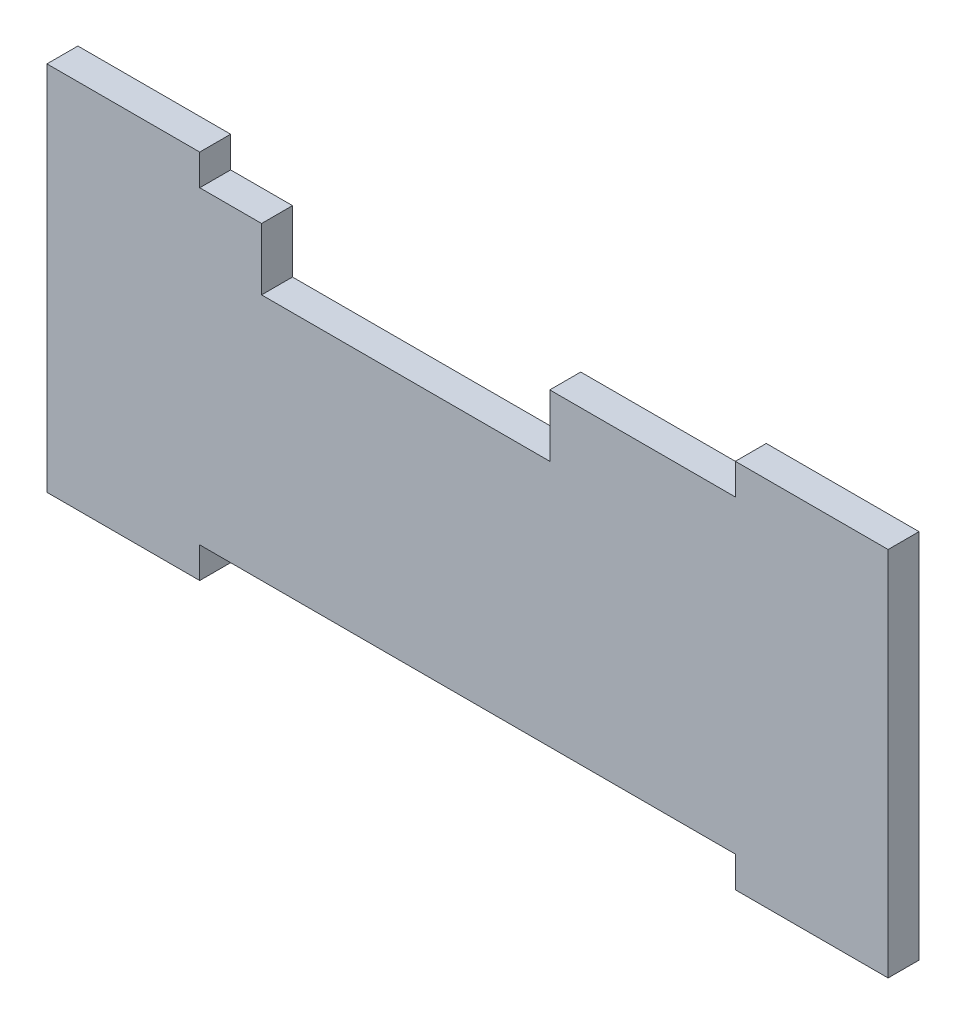
SolidWorks part; units mm, degrees
ref_plane "Front Plane" through (0, 0, 0) normal (0, 0, 1) x (1, 0, 0)
ref_plane "Top Plane" through (0, 0, 0) normal (0, 1, 0) x (1, 0, 0)
ref_plane "Right Plane" through (0, 0, 0) normal (1, 0, 0) x (0, 0, -1)
sketch "Sketch1" plane through (0, 0, 0) normal (0, 0, 1) x (1, 0, 0)
  line L1 (-68, 50) -> (68, 50)
  line L2 (-68, 50) -> (-68, 0)
  line L3 (-68, 0) -> (68, 0)
  line L4 (68, 50) -> (68, 0)
  point P4 (0, 0)
  dimension "D1" = 136
  dimension "D2" = 50
extrude "Boss-Extrude1" add sketch "Sketch1" along normal blind 5
sketch "Sketch2" plane through (0, 50, 0) normal (0, 1, 0) x (1, 0, 0)
  line L0 (68, -5) -> (-68, -5) construction
  line L1 (-68, 0) -> (-43.3, 0)
  line L2 (-68, 0) -> (-68, -5)
  line L3 (-68, -5) -> (-43.3, -5)
  line L4 (-43.3, 0) -> (-43.3, -5)
  line L6 (68, 0) -> (43.3, 0)
  line L7 (68, 0) -> (68, -5)
  line L8 (68, -5) -> (43.3, -5)
  line L9 (43.3, 0) -> (43.3, -5)
  dimension "D1" = 24.7
  dimension "D2" = 24.7
extrude "Boss-Extrude2" add sketch "Sketch2" along normal blind 5
sketch "Sketch3" plane through (0, 0, 0) normal (0, -1, 0) x (1, 0, 0)
  line L0 (-68, 0) -> (68, 0) construction
  line L1 (-68, 5) -> (-43.3, 5)
  line L2 (-68, 5) -> (-68, 0)
  line L3 (-68, 0) -> (-43.3, 0)
  line L4 (-43.3, 5) -> (-43.3, 0)
  line L6 (68, 5) -> (43.3, 5)
  line L7 (68, 5) -> (68, 0)
  line L8 (68, 0) -> (43.3, 0)
  line L9 (43.3, 5) -> (43.3, 0)
  dimension "D1" = 24.7
  dimension "D2" = 24.7
extrude "Boss-Extrude3" add sketch "Sketch3" along normal blind 5
sketch "Sketch4" plane through (0, 0, 5) normal (0, 0, 1) x (1, 0, 0)
  line L0 (43.3, 50) -> (-43.3, 50) construction
  line L1 (-33.3, 50) -> (13.3, 50)
  line L2 (-33.3, 50) -> (-33.3, 40)
  line L3 (-33.3, 40) -> (13.3, 40)
  line L4 (13.3, 50) -> (13.3, 40)
  line L5 (-43.3, 55) -> (-43.3, 50) construction
  line L6 (43.3, 55) -> (43.3, 50) construction
  dimension "D1" = 10
  dimension "D2" = 10
  dimension "D3" = 30
extrude "Cut-Extrude1" cut sketch "Sketch4" against normal up to surface (5 mm away) up to face at (0, 25, 0)
